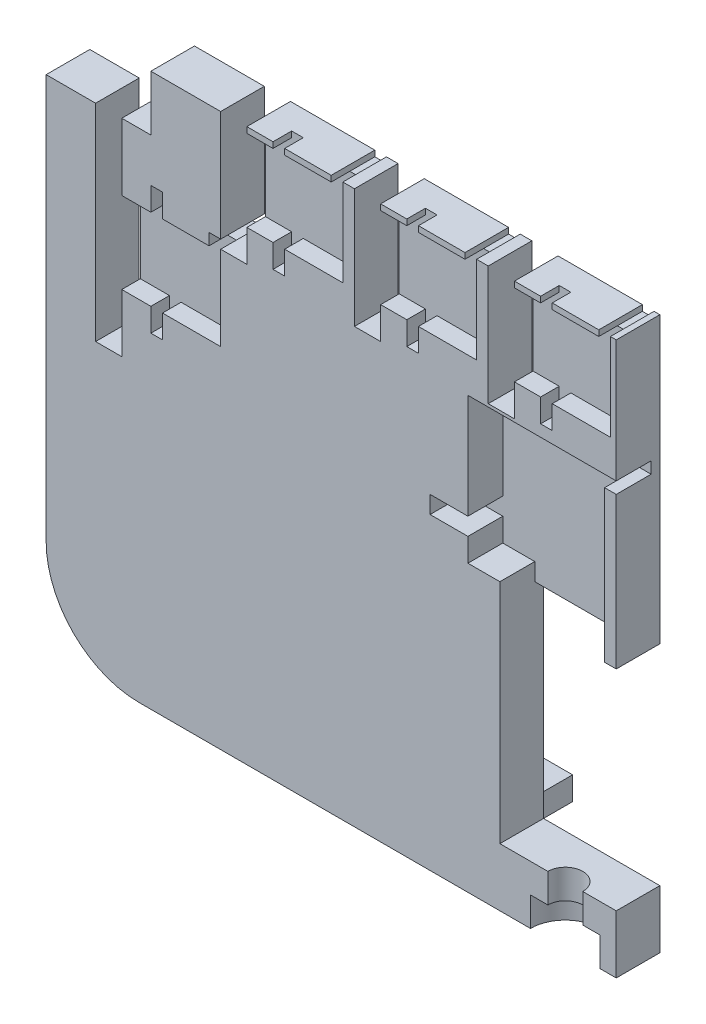
SolidWorks part; units mm, degrees
ref_plane "Front Plane" through (0, 0, 0) normal (0, 0, 1) x (1, 0, 0)
ref_plane "Top Plane" through (0, 0, 0) normal (0, 1, 0) x (1, 0, 0)
ref_plane "Right Plane" through (0, 0, 0) normal (1, 0, 0) x (0, 0, -1)
sketch "Sketch1" plane through (0, 0, 0) normal (0, 0, 1) x (1, 0, 0)
  line L1 (-33, -47.5) -> (49, -47.5)
  line L2 (-49, -31.5) -> (-49, 47.5)
  line L3 (-49, 47.5) -> (27, 47.5)
  line L4 (49, -47.5) -> (49, -29.5)
  line L5 (-49, -47.5) -> (49, 47.5) construction
  line L6 (-49, 47.5) -> (49, -47.5) construction
  line L10 (49, 2.5) -> (31.5, 2.5)
  line L11 (31.5, 2.5) -> (31.5, -29.5)
  line L12 (31.5, -29.5) -> (49, -29.5)
  line L13 (49, 2.5) -> (49, 47.5)
  line L14 (30, 47.5) -> (49, 47.5)
  line L16 (30, 47.5) -> (30, 30.5)
  line L17 (30, 30.5) -> (27, 30.5)
  line L18 (27, 47.5) -> (27, 30.5)
  arc A0 (-33, -47.5) -> (-49, -31.5) centre (-33, -31.5) cw
  point P0 (0, 0)
  point P15 (30, 39)
  dimension "D3" = 16
  dimension "D1" = 98
  dimension "D2" = 95
  dimension "D4" = 18
  dimension "D5" = 17.5
  dimension "D6" = 32
  dimension "D7" = 17
  dimension "D8" = 19
  dimension "D9" = 3
extrude "Boss-Extrude1" add sketch "Sketch1" along normal blind 7.5
sketch "Sketch2" plane through (0, 0, 7.5) normal (0, 0, 1) x (1, 0, 0)
  line L0 (30, 40) -> (31, 40)
  line L1 (30, 47.5) -> (30, 30.5) construction
  line L2 (31, 40) -> (31, 32.5)
  line L3 (31, 32.5) -> (36, 32.5)
  line L4 (36, 32.5) -> (36, 28.5)
  line L5 (36, 28.5) -> (38, 28.5)
  line L6 (38, 28.5) -> (38, 32.5)
  line L7 (38, 32.5) -> (48, 32.5)
  line L8 (48, 32.5) -> (48, 46.5)
  line L9 (48, 46.5) -> (38, 46.5)
  line L10 (31, 46.5) -> (31, 45)
  line L11 (31, 45) -> (30, 45)
  line L12 (30, 45) -> (30, 40)
  line L13 (-16, 40) -> (-15, 40)
  line L14 (36, 46.5) -> (36, 47.5)
  line L15 (49, 47.5) -> (30, 47.5) construction
  line L16 (36, 47.5) -> (38, 47.5)
  line L17 (38, 47.5) -> (38, 46.5)
  line L19 (36, 46.5) -> (31, 46.5)
  line L20 (7, 40) -> (8, 40)
  line L21 (8, 40) -> (8, 32.5)
  line L22 (8, 32.5) -> (13, 32.5)
  line L23 (13, 32.5) -> (13, 28.5)
  line L24 (13, 28.5) -> (15, 28.5)
  line L25 (15, 28.5) -> (15, 32.5)
  line L26 (15, 32.5) -> (25, 32.5)
  line L27 (25, 32.5) -> (25, 46.5)
  line L28 (25, 46.5) -> (15, 46.5)
  line L29 (8, 46.5) -> (8, 45)
  line L30 (8, 45) -> (7, 45)
  line L31 (7, 45) -> (7, 40)
  line L32 (13, 46.5) -> (13, 47.5)
  line L33 (13, 47.5) -> (15, 47.5)
  line L34 (15, 47.5) -> (15, 46.5)
  line L35 (13, 46.5) -> (8, 46.5)
  line L36 (49, 2.5) -> (49, 47.5) construction
  line L37 (27, 47.5) -> (-49, 47.5) construction
  line L38 (-15, 40) -> (-15, 32.5)
  line L39 (-15, 32.5) -> (-10, 32.5)
  line L40 (-10, 32.5) -> (-10, 28.5)
  line L41 (-10, 28.5) -> (-8, 28.5)
  line L42 (-8, 28.5) -> (-8, 32.5)
  line L43 (-8, 32.5) -> (2, 32.5)
  line L44 (2, 32.5) -> (2, 46.5)
  line L45 (2, 46.5) -> (-8, 46.5)
  line L46 (-15, 46.5) -> (-15, 45)
  line L47 (-15, 45) -> (-16, 45)
  line L48 (-16, 45) -> (-16, 40)
  line L49 (-10, 46.5) -> (-10, 47.5)
  line L50 (-10, 47.5) -> (-8, 47.5)
  line L51 (-8, 47.5) -> (-8, 46.5)
  line L52 (-10, 46.5) -> (-15, 46.5)
  point P4 (30, 42.5)
  dimension "D1" = 1
  dimension "D2" = 5
  dimension "D3" = 5
  dimension "D4" = 4
  dimension "D5" = 17
  dimension "D6" = 10
  dimension "D7" = 2
  dimension "D8" = 4
  dimension "D9" = 14
  dimension "D10" = 24
  dimension "D11" = 1
  dimension "D12" = 6
extrude "Cut-Extrude1" cut sketch "Sketch2" against normal blind 3.2
sketch "Sketch3" plane through (0, -47.5, 0) normal (0, -1, 0) x (1, 0, 0)
  line L0 (-33, 7.5) -> (49, 7.5) construction
  line L2 (49, 7.5) -> (31.5, 7.5) construction
  line L4 (34.25, 7.5) -> (46.25, 7.5)
  arc A0 (46.25, 7.5) -> (34.25, 7.5) centre (40.25, 7.5) cw
  point P6 (40.25, 7.5)
  dimension "D2" = 6
  dimension "D1" = 17.5
sketch "Sketch5" plane through (0, 0, 7.5) normal (0, 0, 1) x (1, 0, 0)
  line L0 (7, 47.5) -> (7, 30.5)
  line L1 (13, 47.5) -> (-8, 47.5) construction
  line L2 (7, 30.5) -> (4, 30.5)
  line L3 (4, 30.5) -> (4, 47.5)
  line L4 (4, 47.5) -> (7, 47.5)
  line L5 (27, 30.5) -> (27, 47.5) construction
  line L6 (30, 30.5) -> (27, 30.5) construction
  line L7 (7, 45) -> (7, 40) construction
  line L8 (-16, 47.5) -> (-16, 30.5)
  line L9 (-10, 47.5) -> (-49, 47.5) construction
  line L10 (-16, 30.5) -> (-19, 30.5)
  line L11 (-19, 30.5) -> (-19, 47.5)
  line L12 (-19, 47.5) -> (-16, 47.5)
  line L13 (-16, 45) -> (-16, 40) construction
extrude "Cut-Extrude4" cut sketch "Sketch5" against normal up to next
sketch "Sketch8" plane through (0, 0, 7.5) normal (0, 0, 1) x (1, 0, 0)
  line L0 (-19, 47.5) -> (-49, 47.5) construction
  line L1 (-37, 47.5) -> (-49, 47.5)
  line L2 (-37, 47.5) -> (-37, 10.5)
  line L3 (-37, 10.5) -> (-49, 10.5)
  line L4 (-49, 47.5) -> (-49, 10.5)
  line L5 (-49, 47.5) -> (-49, -31.5) construction
  dimension "D1" = 12
  dimension "D2" = 37
extrude "Cut-Extrude5" cut sketch "Sketch8" against normal up to next
sketch "Sketch9" plane through (0, 0, 7.5) normal (0, 0, 1) x (1, 0, 0)
  line L0 (-37, 20) -> (-36, 20)
  line L1 (-36, 20) -> (-36, 12.5)
  line L2 (-36, 12.5) -> (-31, 12.5)
  line L3 (-31, 12.5) -> (-31, 8.5)
  line L4 (-31, 8.5) -> (-29, 8.5)
  line L5 (-29, 8.5) -> (-29, 12.5)
  line L6 (-29, 12.5) -> (-19, 12.5)
  line L7 (-19, 12.5) -> (-19, 26.5)
  line L8 (-19, 26.5) -> (-29, 26.5)
  line L9 (-36, 26.5) -> (-36, 25)
  line L10 (-36, 25) -> (-37, 25)
  line L11 (-37, 25) -> (-37, 20)
  line L12 (-31, 26.5) -> (-31, 30.5)
  line L13 (-31, 30.5) -> (-29, 30.5)
  line L14 (-29, 30.5) -> (-29, 26.5)
  line L15 (-31, 26.5) -> (-36, 26.5)
  line L16 (-49, 10.5) -> (-37, 10.5) construction
  line L17 (-37, 10.5) -> (-37, 47.5) construction
  point P2 (-37, 22.5)
  dimension "D1" = 14
  dimension "D2" = 17
  dimension "D3" = 10
  dimension "D4" = 2
  dimension "D5" = 5
  dimension "D6" = 4
  dimension "D7" = 7.5
  dimension "D8" = 5
  dimension "D9" = 1
  dimension "D10" = 4
  dimension "D11" = 12
extrude "Cut-Extrude6" cut sketch "Sketch9" against normal blind 3.2
sketch "Sketch10" plane through (0, 10.5, 0) normal (0, 1, 0) x (1, 0, 0)
  line L0 (-49, -7.5) -> (-37, -7.5) construction
  line L1 (-49, 0) -> (-39, 0)
  line L2 (-49, 0) -> (-49, -7.5)
  line L3 (-49, -7.5) -> (-39, -7.5)
  line L4 (-39, 0) -> (-39, -7.5)
  dimension "D1" = 10
extrude "Boss-Extrude2" add sketch "Sketch10" along normal blind 27.4864
sketch "Sketch11" plane through (0, 30.5, 0) normal (0, 1, 0) x (1, 0, 0)
  line L1 (-19, 0) -> (-16, 0)
  line L2 (-19, 0) -> (-19, -7.5)
  line L3 (-19, -7.5) -> (-16, -7.5)
  line L4 (-16, 0) -> (-16, -7.5)
  line L5 (4, 0) -> (7, 0)
  line L6 (4, 0) -> (4, -7.5)
  line L7 (4, -7.5) -> (7, -7.5)
  line L8 (7, 0) -> (7, -7.5)
  line L9 (27, 0) -> (30, 0)
  line L10 (27, 0) -> (27, -7.5)
  line L11 (27, -7.5) -> (30, -7.5)
  line L12 (30, 0) -> (30, -7.5)
extrude "Cut-Extrude7" cut sketch "Sketch11" against normal blind 3.5
sketch "Sketch12" plane through (0, 10.5, 0) normal (0, 1, 0) x (1, 0, 0)
  line L1 (-37, 0) -> (-39, 0)
  line L2 (-37, 0) -> (-37, -7.5)
  line L3 (-37, -7.5) -> (-39, -7.5)
  line L4 (-39, 0) -> (-39, -7.5)
extrude "Cut-Extrude8" cut sketch "Sketch12" against normal blind 4
sketch "Sketch13" plane through (0, 6.5, 0) normal (0, 1, 0) x (1, 0, 0)
  line L1 (-39, 0) -> (-37, 0)
  line L2 (-39, 0) -> (-39, -7.5)
  line L3 (-39, -7.5) -> (-37, -7.5)
  line L4 (-37, 0) -> (-37, -7.5)
extrude "Cut-Extrude9" cut sketch "Sketch13" against normal blind 4
sketch "Sketch14" plane through (-37, 0, 0) normal (-1, 0, 0) x (0, 0, 1)
  line L0 (7.5, 25) -> (7.5, 47.5) construction
  line L1 (0, 47.5) -> (7.5, 47.5)
  line L2 (0, 47.5) -> (0, 38)
  line L3 (0, 38) -> (7.5, 38)
  line L4 (7.5, 47.5) -> (7.5, 38)
  dimension "D1" = 13
extrude "Cut-Extrude10" cut sketch "Sketch14" against normal blind 6
ref_plane "Plane1" through (0, 0, 17.5) normal (0, 0, 1) x (1, 0, 0)
sketch "Sketch16" plane through (0, 37.9864, 0) normal (0, 1, 0) x (1, 0, 0)
  line L0 (-39, 0) -> (-49, 0) construction
  line L1 (-40.5, 0) -> (-39, 0)
  line L2 (-40.5, 0) -> (-40.5, -7.5)
  line L3 (-40.5, -7.5) -> (-39, -7.5)
  line L4 (-39, 0) -> (-39, -7.5)
  line L5 (-49, -7.5) -> (-39, -7.5) construction
  line L6 (-49, 0) -> (-49, -7.5) construction
  dimension "D1" = 8.5
  dimension "D2" = 10
extrude "Cut-Extrude12" cut sketch "Sketch16" against normal blind 35.4864
sketch "Sketch18" plane through (0, 0, 7.5) normal (0, 0, 1) x (1, 0, 0)
  line L0 (23.5, 5.5) -> (23.5, 1.5)
  line L1 (23.5, 26.5) -> (47, 26.5)
  line L2 (23.5, 26.5) -> (23.5, 8.5)
  line L3 (23.5, 1.5) -> (47, 1.5)
  line L4 (47, 24.5) -> (47, 1.5)
  line L5 (23.5, 5.5) -> (17, 5.5)
  line L7 (23.5, 8.5) -> (17, 8.5)
  line L8 (17, 5.5) -> (17, 8.5)
  line L9 (49, 2.5) -> (49, 47.5) construction
  line L11 (27, 27) -> (30, 27) construction
  line L12 (47, 26.5) -> (49, 26.5)
  line L14 (47, 24.5) -> (49, 24.5)
  line L15 (49, 26.5) -> (49, 24.5)
  point P5 (23.5, 5.5)
  dimension "D1" = 23.5
  dimension "D2" = 25
  dimension "D3" = 4
  dimension "D4" = 6.5
  dimension "D5" = 3
  dimension "D6" = 2
  dimension "D7" = 2
  dimension "D8" = 23.5
  dimension "D9" = 0.5
extrude "Cut-Extrude13" cut sketch "Sketch18" against normal blind 6
sketch "Sketch19" plane through (0, 0, 0) normal (0, 0, -1) x (-1, 0, 0)
  line L1 (-31.5, 2.5) -> (-49, 2.5)
  line L2 (-31.5, 2.5) -> (-31.5, -29.5)
  line L3 (-31.5, -29.5) -> (-49, -29.5)
  line L4 (-49, 2.5) -> (-49, -29.5)
extrude "Boss-Extrude3" add sketch "Sketch19" against normal blind 7.5 contours L2 L1 L4 L3
extrude "Cut-Extrude14" cut sketch "Sketch18<2>" against normal blind 6
sketch "Sketch18<2>" plane through (0, 0, 7.5) normal (0, 0, 1) x (1, 0, 0) same geometry as "Sketch18"
sketch "Sketch20" plane through (0, 0, 7.5) normal (0, 0, 1) x (1, 0, 0)
  line L0 (47, 1.5) -> (29, 1.5)
  line L5 (23.5, 1.5) -> (47, 1.5) construction
  line L6 (47, 1.5) -> (47, -4.5)
  line L7 (47, -4.5) -> (29, -4.5)
  line L8 (29, -4.5) -> (29, 1.5)
  dimension "D1" = 18
  dimension "D2" = 6
extrude "Cut-Extrude15" cut sketch "Sketch20" against normal blind 6
sketch "Sketch21" plane through (0, 0, 7.5) normal (0, 0, 1) x (1, 0, 0)
  line L0 (49, -4.5) -> (49, -37.5)
  line L1 (49, -47.5) -> (49, 24.5) construction
  line L2 (49, -37.5) -> (29, -37.5)
  line L3 (29, -37.5) -> (29, -4.5)
  line L4 (29, -4.5) -> (49, -4.5)
  line L6 (29, -4.5) -> (47, -4.5) construction
  dimension "D1" = 33
  dimension "D2" = 20
extrude "Cut-Extrude16" cut sketch "Sketch21" against normal blind 11
extrude "Cut-Extrude17" cut sketch "Sketch3" against normal blind 5
sketch "Sketch22" plane through (0, -42.5, 0) normal (0, -1, 0) x (1, 0, 0)
  line L0 (46.25, 7.5) -> (34.25, 7.5) construction
  line L1 (37.25, 7.5) -> (43.25, 7.5)
  arc A0 (37.25, 7.5) -> (43.25, 7.5) centre (40.25, 7.5) ccw
  dimension "D1" = 3
extrude "Cut-Extrude18" cut sketch "Sketch22" against normal blind 10
sketch "Sketch23" plane through (0, 0, 0) normal (0, 0, -1) x (-1, 0, 0)
  line L0 (33, -47.5) -> (-49, -47.5) construction
  line L1 (-19, -47.5) -> (31, -47.5)
  line L2 (-19, -47.5) -> (-19, -43.5)
  line L3 (-19, -43.5) -> (31, -43.5)
  line L4 (31, -47.5) -> (31, -43.5)
  line L5 (-49, -47.5) -> (-49, -37.5) construction
  dimension "D1" = 4
  dimension "D2" = 50
  dimension "D3" = 30
extrude "Boss-Extrude4" add sketch "Sketch23" along normal blind 15
sketch "Sketch24" plane through (0, -43.5, 0) normal (0, 1, 0) x (1, 0, 0)
  line L0 (2.3333, 7.5) -> (2.3333, 15) construction
  line L1 (-31, 15) -> (19, 15) construction
  line L2 (2.3333, 7.5) -> (2.3333, 0) construction
  line L3 (-31, 0) -> (19, 0) construction
  line L4 (19, 7.5) -> (2.3333, 7.5) construction
  line L5 (19, 15) -> (19, 0) construction
  line L6 (2.3333, 7.5) -> (-14.3333, 7.5) construction
  line L7 (-14.3333, 7.5) -> (-31, 7.5) construction
  line L8 (-31, 15) -> (-31, 0) construction
  circle A0 centre (2.3333, 7.5) radius 0.5
  circle A1 centre (-14.3333, 7.5) radius 0.5
  dimension "D1" = 1
sketch "Sketch25" plane through (0, -47.5, 0) normal (0, -1, 0) x (-1, 0, 0)
  line L0 (49, -7.5) -> (49, 0) construction
  line L1 (33, -7.5) -> (-34.25, -7.5) construction
  circle A0 centre (-1, 7.5) radius 3.5
  dimension "D2" = 7
  dimension "D1" = 50
  dimension "D3" = 15
extrude "Cut-Extrude19" cut sketch "Sketch25" against normal blind 10
ref_plane "Plane2" through (0, 0, 17.5) normal (0, 0, 1) x (1, 0, 0)
sketch "Sketch26" plane through (0, 0, 0) normal (0, 0, -1) x (-1, 0, 0)
  line L0 (-49, 47.5) -> (-30, 47.5) construction
  line L1 (-31.5, 47.5) -> (-30, 47.5)
  line L2 (-31.5, 47.5) -> (-31.5, 27)
  line L3 (-31.5, 27) -> (-30, 27)
  line L4 (-30, 47.5) -> (-30, 27)
  dimension "D1" = 1.5
extrude "Cut-Extrude20" cut sketch "Sketch26" against normal blind 8 contours L2 L1 L4 L3
sketch "Sketch27" plane through (0, 0, 0) normal (0, 0, -1) x (-1, 0, 0)
  line L0 (-27, 47.5) -> (-7, 47.5) construction
  line L1 (-8.5, 47.5) -> (-7, 47.5)
  line L2 (-8.5, 47.5) -> (-8.5, 27)
  line L3 (-8.5, 27) -> (-7, 27)
  line L4 (-7, 47.5) -> (-7, 27)
  line L5 (-7, 27) -> (-7, 47.5) construction
  line L7 (-19, -47.5) -> (-49, -47.5) construction
  dimension "D1" = 1.5
  dimension "D2" = 74.5
extrude "Cut-Extrude21" cut sketch "Sketch27" against normal blind 8 contours L2 L1 L4 L3
sketch "Sketch28" plane through (0, 0, 0) normal (0, 0, -1) x (-1, 0, 0)
  line L0 (-4, 47.5) -> (16, 47.5) construction
  line L1 (14.5, 47.5) -> (16, 47.5)
  line L2 (14.5, 47.5) -> (14.5, 27)
  line L3 (14.5, 27) -> (16, 27)
  line L4 (16, 47.5) -> (16, 27)
  dimension "D1" = 1.5
extrude "Cut-Extrude22" cut sketch "Sketch28" against normal blind 8 contours L2 L1 L4 L3
ref_plane "Plane3" through (-37, 2.5, 0) normal (0, 1, 0) x (1, 0, 0)
ref_plane "Plane5" through (-40.5, 37.9864, 0) normal (-1, 0, 0) x (0, 0, 1)
sketch "Sketch35" plane through (0, 0, 7.5) normal (0, 0, 1) x (1, 0, 0)
  line L0 (4, 47.5) -> (-8, 47.5) construction
  line L1 (-19, 26.5) -> (-21, 26.5)
  line L2 (-19, 26.5) -> (-19, 28.5)
  line L3 (-19, 28.5) -> (-21, 28.5)
  line L4 (-21, 26.5) -> (-21, 28.5)
  line L5 (2, 46.5) -> (0, 46.5)
  line L6 (2, 46.5) -> (2, 47.5)
  line L7 (2, 47.5) -> (0, 47.5)
  line L8 (0, 46.5) -> (0, 47.5)
  line L9 (27, 47.5) -> (15, 47.5) construction
  line L10 (25, 46.5) -> (23, 46.5)
  line L11 (25, 46.5) -> (25, 47.5)
  line L12 (25, 47.5) -> (23, 47.5)
  line L13 (23, 46.5) -> (23, 47.5)
  line L14 (49, 47.5) -> (38, 47.5) construction
  line L15 (48, 46.5) -> (46, 46.5)
  line L16 (48, 46.5) -> (48, 47.5)
  line L17 (48, 47.5) -> (46, 47.5)
  line L18 (46, 46.5) -> (46, 47.5)
  dimension "D1" = 2
  dimension "D2" = 2
  dimension "D3" = 2
  dimension "D4" = 2
  dimension "D5" = 2
extrude "Cut-Extrude25" cut sketch "Sketch35" against normal up to next
sketch "Sketch36" plane through (0, 38, 0) normal (0, 1, 0) x (1, 0, 0)
  line L0 (-31, 0) -> (-37, 0) construction
  line L1 (-37, -7.5) -> (-36, -7.5)
  line L2 (-37, -7.5) -> (-37, 0)
  line L3 (-37, 0) -> (-36, 0)
  line L4 (-36, -7.5) -> (-36, 0)
  line L5 (-37, -7.5) -> (-36, -7.5) construction
  dimension "D1" = 1
extrude "Cut-Extrude26" cut sketch "Sketch36" against normal up to surface (35.5 mm away) up to face at (-38.75, 2.5, 3.75)
sketch "Sketch37" plane through (49, 0, 0) normal (1, 0, 0) x (0, 0, -1)
  line L0 (0, -4.5) -> (0, 47.5) construction
  line L1 (-7.5, -4.5) -> (0, -4.5)
  line L2 (-7.5, -4.5) -> (-7.5, -1.5)
  line L3 (-7.5, -1.5) -> (0, -1.5)
  line L4 (0, -4.5) -> (0, -1.5)
  point P7 (-7.5, -3)
  dimension "D1" = 3
extrude "Cut-Extrude27" cut sketch "Sketch37" against normal up to surface (20 mm away) up to face at (29, -13.5, 3)
ref_plane "Plane6" through (0, 0, 17.5) normal (0, 0, 1) x (1, 0, 0)
